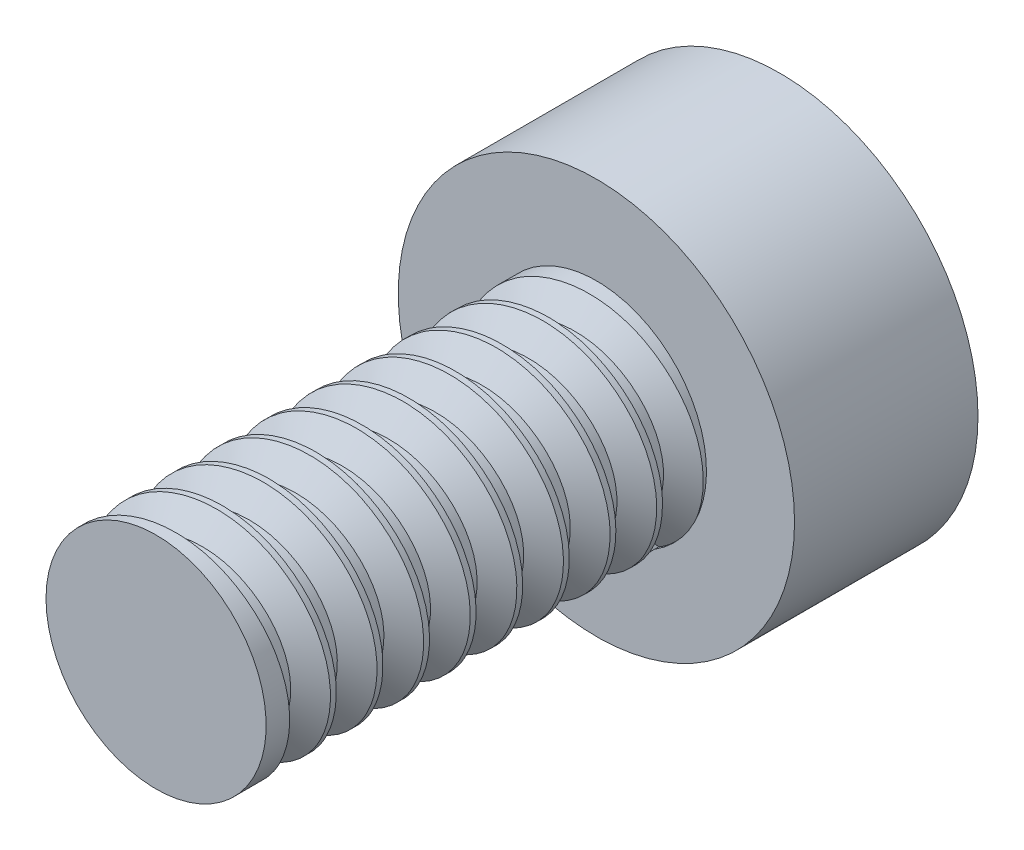
SolidWorks part; units mm, degrees
ref_plane "前视基准面" through (0, 0, 0) normal (0, 0, 1) x (1, 0, 0)
ref_plane "上视基准面" through (0, 0, 0) normal (0, 1, 0) x (1, 0, 0)
ref_plane "右视基准面" through (0, 0, 0) normal (1, 0, 0) x (0, 0, -1)
sketch "草图1" plane through (0, 0, 0) normal (0, 0, 1) x (1, 0, 0)
  circle A0 centre (0, 0) radius 2.7
  dimension "D1" = 5.4
extrude "凸台-拉伸1" add sketch "草图1" along normal blind 2.5
sketch "草图2" plane through (0, 0, 2.5) normal (0, 0, 1) x (1, 0, 0)
  circle A0 centre (0, 0) radius 1.5
  dimension "D1" = 3
extrude "凸台-拉伸2" add sketch "草图2" along normal blind 6
thread "螺纹线1" pitch 0.635 method cut profile "螺纹线轮廓1" start angle 0, offset 0, length 5.5, pitch 0.635, diameter 3
ref_plane "基准面4" through (-1.5, 0, 8.5) normal (0, -1, 0) x (-1, 0, 0)
sketch "螺纹线轮廓1" plane through (-1.5, 0, 8.5) normal (0, -1, 0) x (-1, 0, 0)
  line L0 (0, 0) -> (0, 0.635) construction
  line L11 (0, 0) -> (0, 0.5556)
  line L12 (0, 0.5556) -> (-0.3437, 0.3572)
  line L13 (-0.3437, 0.3572) -> (-0.3437, 0.1984)
  line L15 (-0.3437, 0.1984) -> (0, 0)
  line L17 (-0.3437, 0.2778) -> (0, 0.2778) construction
  point P2 (0, 0)
  dimension "Pitch" = 0.635
  dimension "Profile_Angle" = 60
  dimension "Profile_Land" = 0.1588
  dimension "Profile_Height" = 0.3437
sketch "草图6" plane through (0, 0, 0) normal (0, 0, -1) x (-1, 0, 0)
  line L1 (1.5433, -0.7863) -> (1.4526, 0.9434)
  line L2 (1.4526, 0.9434) -> (-0.0907, 1.7297)
  line L3 (-0.0907, 1.7297) -> (-1.5433, 0.7863)
  line L4 (-1.5433, 0.7863) -> (-1.4526, -0.9434)
  line L5 (-1.4526, -0.9434) -> (0.0907, -1.7297)
  line L6 (0.0907, -1.7297) -> (1.5433, -0.7863)
  circle A0 centre (0, 0) radius 1.5 construction
  dimension "D1" = 3
extrude "切除-拉伸1" cut sketch "草图6" against normal blind 0.5
